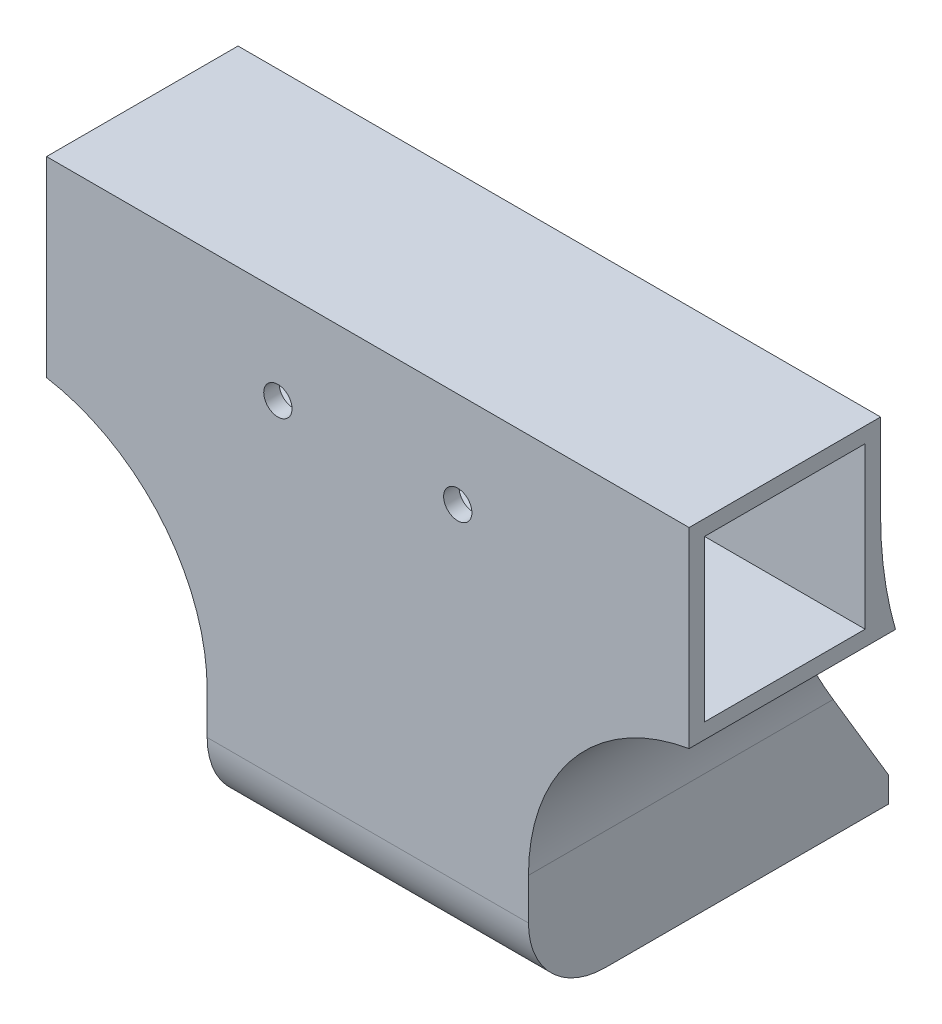
SolidWorks part; units mm, degrees
ref_plane "Front" through (0, 0, 0) normal (0, 0, 1) x (1, 0, 0)
ref_plane "Top" through (0, 0, 0) normal (0, 1, 0) x (1, 0, 0)
ref_plane "Right" through (0, 0, 0) normal (1, 0, 0) x (0, 0, -1)
sketch "Эскиз1" plane through (0, 0, 0) normal (1, 0, 0) x (0, 0, -1)
  line L1 (-12.5, -12.5) -> (12.5, -12.5)
  line L2 (-12.5, -12.5) -> (-12.5, 12.5)
  line L3 (-12.5, 12.5) -> (12.5, 12.5)
  line L4 (12.5, -12.5) -> (12.5, 12.5)
  line L5 (-12.5, -12.5) -> (12.5, 12.5) construction
  line L6 (-12.5, 12.5) -> (12.5, -12.5) construction
  point P0 (0, 0)
  dimension "D1" = 25
  dimension "D2" = 25
extrude "Вытянуть-Тонкостенный1" add sketch "Эскиз1" along normal blind 100 thin thin type one direction wall 2.4
sketch "Эскиз2" plane through (0, -14.9, 0) normal (0, -1, 0) x (1, 0, 0)
  line L0 (50, 14.9) -> (50, -14.9) construction
  line L1 (100, 14.9) -> (0, 14.9) construction
  line L2 (100, -14.9) -> (0, -14.9) construction
  line L4 (25, 0.9) -> (75, 0.9)
  line L5 (25, 0.9) -> (25, 14.9)
  line L6 (25, 14.9) -> (75, 14.9)
  line L7 (75, 0.9) -> (75, 14.9)
  line L8 (25, 0.9) -> (75, 14.9) construction
  line L9 (25, 14.9) -> (75, 0.9) construction
  point P6 (50, 7.9)
  dimension "D1" = 50
  dimension "D2" = 14
extrude "Бобышка-Вытянуть1" add sketch "Эскиз2" along normal blind 48
sketch "Эскиз3" plane through (0, 0, 0.9) normal (0, 0, -1) x (-1, 0, 0)
  line L0 (-25, -62.9) -> (-25, -14.9) construction
  line L1 (-75, -62.9) -> (-25, -62.9)
  line L2 (-75, -62.9) -> (-75, -58.9)
  line L3 (-75, -58.9) -> (-25, -58.9)
  line L4 (-25, -62.9) -> (-25, -58.9)
  dimension "D1" = 4
extrude "Бобышка-Вытянуть2" add sketch "Эскиз3" along normal blind 42
sketch "Эскиз4" plane through (75, 0, 0) normal (1, 0, 0) x (0, 0, -1)
  line L0 (14.9, -14.9) -> (41.1, -58.9)
  line L1 (41.1, -58.9) -> (-0.9, -58.9)
  line L2 (-0.9, -58.9) -> (-0.9, -14.9)
  line L3 (-0.9, -14.9) -> (14.9, -14.9)
extrude "Бобышка-Вытянуть3" add sketch "Эскиз4" against normal blind 4
sketch "Эскиз5" plane through (25, 0, 0) normal (-1, 0, 0) x (0, 0, 1)
  line L0 (-41.1, -58.9) -> (-14.9, -14.9)
  line L1 (-14.9, -14.9) -> (0.9, -14.9)
  line L2 (0.9, -14.9) -> (0.9, -58.9)
  line L3 (0.9, -58.9) -> (-41.1, -58.9)
extrude "Бобышка-Вытянуть4" add sketch "Эскиз5" against normal blind 4
fillet "Скругление2" radius 30 2 edges at (75, -14.9, 0) (25, -14.9, 0)
sketch "Эскиз6" plane through (0, -62.9, 0) normal (0, -1, 0) x (1, 0, 0)
  line L0 (50, 14.9) -> (50, -41.1) construction
  line L1 (75, 14.9) -> (25, 14.9) construction
  line L2 (75, -41.1) -> (25, -41.1) construction
  line L4 (34.5, -35.6) -> (65.5, -35.6) construction
  line L5 (34.5, -35.6) -> (34.5, -4.6) construction
  line L6 (34.5, -4.6) -> (65.5, -4.6) construction
  line L7 (65.5, -35.6) -> (65.5, -4.6) construction
  line L8 (34.5, -35.6) -> (65.5, -4.6) construction
  line L9 (34.5, -4.6) -> (65.5, -35.6) construction
  circle A0 centre (50, -20.1) radius 11.5
  circle A1 centre (34.5, -4.6) radius 1.6
  circle A2 centre (65.5, -4.6) radius 1.6
  circle A3 centre (34.5, -35.6) radius 1.6
  circle A4 centre (65.5, -35.6) radius 1.6
  dimension "D1" = 31
  dimension "D3" = 35
  dimension "D2" = 31
extrude "Вырез-Вытянуть1" cut sketch "Эскиз6" against normal up to next
fillet "Скругление3" radius 12 1 edges at (50, -62.9, 14.9)
fillet "Скругление4" radius 60 2 edges at (14.5, -14.9, -14.9) (85.5, -14.9, -14.9)
sketch "Эскиз7" plane through (0, 0, -14.9) normal (0, 0, -1) x (-1, 0, 0)
  line L0 (0, 0) -> (-100, 0) construction
  line L1 (-100, 1.6109) -> (-100, -14.9) construction
  line L2 (-100, 1.6109) -> (-100, 14.9) construction
  line L3 (0, 1.6109) -> (0, 14.9) construction
  circle A0 centre (-64, 0) radius 2.2
  circle A1 centre (-36, 0) radius 2.2
  dimension "D1" = 36
  dimension "D2" = 36
extrude "Вырез-Вытянуть2" cut sketch "Эскиз7" against normal through all
fillet "Скругление5" radius 2 1 edges at (50, -14.9, -14.9)
sketch "Эскиз8" plane through (25, 0, 0) normal (-1, 0, 0) x (0, 0, 1)
  line L0 (2.9, -62.9) -> (-41.1, -62.9) construction
  line L1 (-41.1, -62.9) -> (-41.1, -58.9) construction
  circle A0 centre (-25.1, -60.9) radius 1.2
  circle A1 centre (2.9, -60.9) radius 1.2
  dimension "D1" = 28
  dimension "D2" = 2
  dimension "D3" = 16
extrude "Вырез-Вытянуть3" cut sketch "Эскиз8" against normal blind 5
sketch "Эскиз9" plane through (25, 0, 0) normal (-1, 0, 0) x (0, 0, 1)
  line L0 (2.9, -62.9) -> (-41.1, -62.9) construction
  line L1 (-27.3361, -62.9) -> (-22.8639, -62.9)
  line L2 (2.9, -62.9) -> (0.6464, -62.9)
  arc A0 (-22.8639, -62.9) -> (-27.3361, -62.9) centre (-25.1, -60.9) ccw
  arc A1 (5.5135, -62.3995) -> (0.6464, -62.9) centre (2.9, -60.9) ccw
  circle A3 centre (-25.1, -60.9) radius 1.2
  circle A4 centre (2.9, -60.9) radius 1.2
  arc A5 (2.9, -62.9) -> (5.5135, -62.3995) centre (-0.2425, -39.4183) ccw
extrude "Бобышка-Вытянуть5" add sketch "Эскиз9" along normal blind 1
fillet "Скругление6" radius 1 2 edges at (25, -57.9027, 2.5918) (25, -57.9, -25.1)
